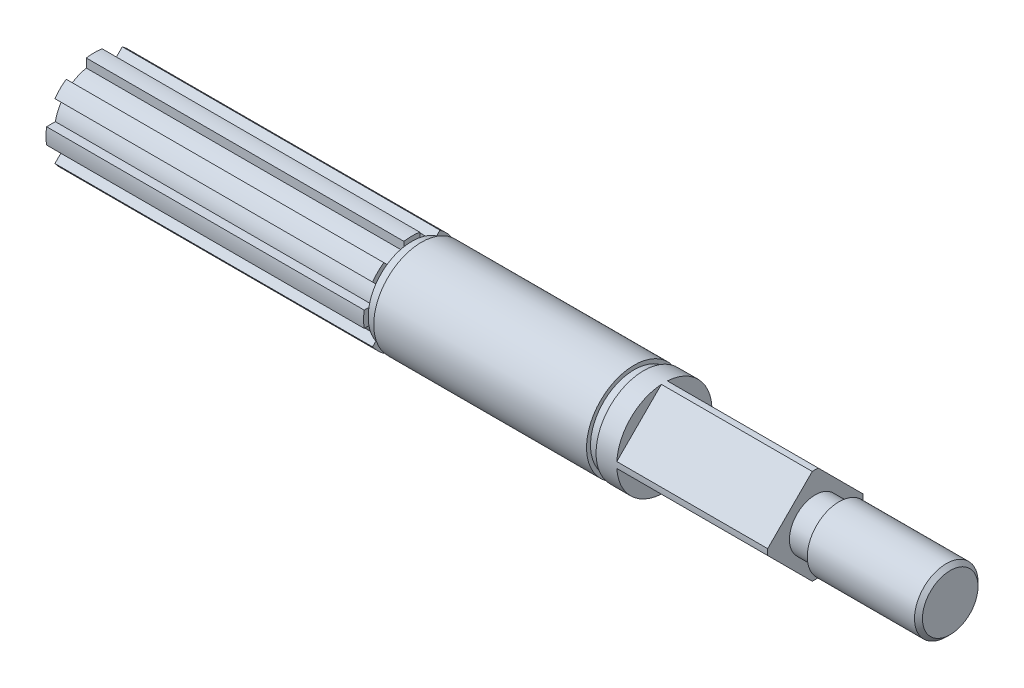
SolidWorks part; units mm, degrees
ref_plane "前视基准面" through (0, 0, 0) normal (0, 0, 1) x (1, 0, 0)
ref_plane "上视基准面" through (0, 0, 0) normal (0, 1, 0) x (1, 0, 0)
ref_plane "右视基准面" through (0, 0, 0) normal (1, 0, 0) x (0, 0, -1)
other "Configuration Table"
ref_axis "基准轴1" through (88.99, 0, 0) along (-1, 0, 0)
sketch "草图1" plane through (0, 0, 0) normal (1, 0, 0) x (0, 0, -1)
  circle A0 centre (0, 0) radius 7
extrude "凸台-拉伸1" add sketch "草图1" along normal blind 40
sketch "草图2" plane through (40, 0, 0) normal (1, 0, 0) x (0, 0, -1)
  line L0 (1, 6) -> (1, 4.899)
  line L1 (-1, 6) -> (-1, 4.899)
  line L2 (3.8268, 9.2388) -> (1.9134, 4.6194)
  line L3 (-3.8268, 9.2388) -> (-1.9134, 4.6194)
  arc A0 (-1.9134, 4.6194) -> (-1, 4.899) centre (0, 0) cw
  arc A1 (1, 4.899) -> (1.9134, 4.6194) centre (0, 0) cw
  arc A2 (-3.8268, 9.2388) -> (3.8268, 9.2388) centre (0, 0) cw
  arc A3 (1, 6) -> (-1, 6) centre (0, 0) ccw
extrude "切除-拉伸1" cut sketch "草图2" against normal blind 40
pattern_circular "阵列(圆周)1" count 8 every 45 about axis through (88.99, 0, 0) along (-1, 0, 0) of "切除-拉伸1"
sketch "草图3" plane through (40, 0, 0) normal (1, 0, 0) x (0, 0, -1)
  circle A0 centre (0, 0) radius 5.5
extrude "凸台-拉伸2" add sketch "草图3" along normal blind 1.2
sketch "草图4" plane through (41.2, 0, 0) normal (1, 0, 0) x (0, 0, -1)
  circle A0 centre (0, 0) radius 6
extrude "凸台-拉伸3" add sketch "草图4" along normal blind 26.8
sketch "草图5" plane through (68, 0, 0) normal (1, 0, 0) x (0, 0, -1)
  circle A0 centre (0, 0) radius 5.5
extrude "凸台-拉伸4" add sketch "草图5" along normal blind 1.2
sketch "草图6" plane through (69.2, 0, 0) normal (1, 0, 0) x (0, 0, -1)
  circle A0 centre (0, 0) radius 6
extrude "凸台-拉伸5" add sketch "草图6" along normal blind 2.6
sketch "草图7" plane through (71.8, 0, 0) normal (1, 0, 0) x (0, 0, -1)
  line L5 (0, -6.364) -> (6.364, 0)
  line L6 (6.364, 0) -> (0, 6.364)
  line L7 (0, 6.364) -> (-6.364, 0)
  line L8 (-6.364, 0) -> (0, -6.364)
  circle A0 centre (0, 0) radius 4.5 construction
  dimension "D1" = 9
extrude "凸台-拉伸6" add sketch "草图7" along normal blind 19
sketch "草图8" plane through (90.8, 0, 0) normal (1, 0, 0) x (0, 0, -1)
  circle A0 centre (0, 0) radius 3.25
extrude "凸台-拉伸7" add sketch "草图8" along normal blind 3
sketch "草图9" plane through (93.8, 0, 0) normal (1, 0, 0) x (0, 0, -1)
  circle A0 centre (0, 0) radius 4
extrude "凸台-拉伸8" add sketch "草图9" along normal blind 14
chamfer "倒角1" distance 0.5 angle 45 1 edges at (107.8, 0, -4)
sketch "草图10" plane through (71.8, 0, 0) normal (1, 0, 0) x (0, 0, -1)
  circle A0 centre (0, 0) radius 6
extrude "切除-拉伸2" cut sketch "草图10" along normal blind 22 flip side to cut
